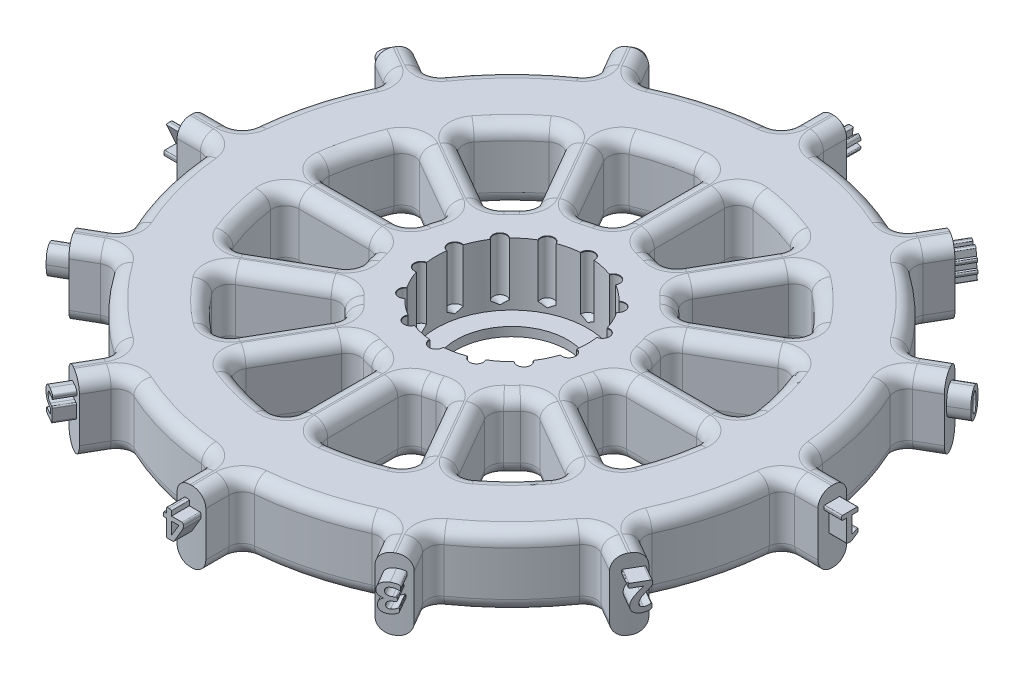
SolidWorks part; units mm, degrees
note: '?' marks a value the reader was unsure of.
ref_plane "Front Plane" through (0, 0, 0) normal (0, 0, 1) x (1, 0, 0)
ref_plane "Top Plane" through (0, 0, 0) normal (0, 1, 0) x (1, 0, 0)
ref_plane "Right Plane" through (0, 0, 0) normal (1, 0, 0) x (0, 0, -1)
sketch "Sketch1" plane through (0, 0, 0) normal (0, 1, 0) x (1, 0, 0)
  line L1 (1.6138, 23.9457) -> (1.6138, 6.038)
  line L4 (0, 36.7262) -> (0, 36) construction
  line L5 (13.3705, 19.9306) -> (4.4167, 4.4222)
  line L6 (-1.6138, 23.9457) -> (-1.6138, 6.038)
  line L7 (1.6138, 31.9593) -> (1.6138, 35.9638)
  line L8 (-1.6138, 31.9593) -> (-1.6138, 35.9638)
  line L9 (10.5752, 21.5445) -> (1.6214, 6.036)
  line L10 (17.3773, 26.8706) -> (19.3795, 30.3387)
  line L11 (14.582, 28.4845) -> (16.5843, 31.9525)
  line L12 (21.5445, 10.5752) -> (6.036, 1.6214)
  line L13 (19.9306, 13.3705) -> (4.4222, 4.4167)
  line L14 (28.4845, 14.582) -> (31.9525, 16.5843)
  line L15 (26.8706, 17.3773) -> (30.3387, 19.3795)
  line L16 (23.9457, -1.6138) -> (6.038, -1.6138)
  line L17 (23.9457, 1.6138) -> (6.038, 1.6138)
  line L18 (31.9593, -1.6138) -> (35.9638, -1.6138)
  line L19 (31.9593, 1.6138) -> (35.9638, 1.6138)
  line L20 (19.9306, -13.3705) -> (4.4222, -4.4167)
  line L21 (21.5445, -10.5752) -> (6.036, -1.6214)
  line L22 (26.8706, -17.3773) -> (30.3387, -19.3795)
  line L23 (28.4845, -14.582) -> (31.9525, -16.5843)
  line L24 (10.5752, -21.5445) -> (1.6214, -6.036)
  line L25 (13.3705, -19.9306) -> (4.4167, -4.4222)
  line L26 (14.582, -28.4845) -> (16.5843, -31.9525)
  line L27 (17.3773, -26.8706) -> (19.3795, -30.3387)
  line L28 (-1.6138, -23.9457) -> (-1.6138, -6.038)
  line L29 (1.6138, -23.9457) -> (1.6138, -6.038)
  line L30 (-1.6138, -31.9593) -> (-1.6138, -35.9638)
  line L31 (1.6138, -31.9593) -> (1.6138, -35.9638)
  line L32 (-13.3705, -19.9306) -> (-4.4167, -4.4222)
  line L33 (-10.5752, -21.5445) -> (-1.6214, -6.036)
  line L34 (-17.3773, -26.8706) -> (-19.3795, -30.3387)
  line L35 (-14.582, -28.4845) -> (-16.5843, -31.9525)
  line L36 (-21.5445, -10.5752) -> (-6.036, -1.6214)
  line L37 (-19.9306, -13.3705) -> (-4.4222, -4.4167)
  line L38 (-28.4845, -14.582) -> (-31.9525, -16.5843)
  line L39 (-26.8706, -17.3773) -> (-30.3387, -19.3795)
  line L40 (-23.9457, 1.6138) -> (-6.038, 1.6138)
  line L41 (-23.9457, -1.6138) -> (-6.038, -1.6138)
  line L42 (-31.9593, 1.6138) -> (-35.9638, 1.6138)
  line L43 (-31.9593, -1.6138) -> (-35.9638, -1.6138)
  line L44 (-19.9306, 13.3705) -> (-4.4222, 4.4167)
  line L45 (-21.5445, 10.5752) -> (-6.036, 1.6214)
  line L46 (-26.8706, 17.3773) -> (-30.3387, 19.3795)
  line L47 (-28.4845, 14.582) -> (-31.9525, 16.5843)
  line L48 (-10.5752, 21.5445) -> (-1.6214, 6.036)
  line L49 (-13.3705, 19.9306) -> (-4.4167, 4.4222)
  line L50 (-14.582, 28.4845) -> (-16.5843, 31.9525)
  line L51 (-17.3773, 26.8706) -> (-19.3795, 30.3387)
  line L52 (1.6138, 23.9457) -> (1.6138, 6.038)
  circle A0 centre (0, 0) radius 36
  circle A1 centre (0, 0) radius 6.25
  circle A3 centre (0, 0) radius 32
  arc A5 (-1.6138, 6.038) -> (1.6138, 6.038) centre (0, 0) cw
  arc A6 (10.5752, 21.5445) -> (1.6138, 23.9457) centre (0, 0) ccw
  arc A7 (-1.6138, 31.9593) -> (1.6138, 31.9593) centre (0, 0) cw
  arc A8 (-1.6138, 35.9638) -> (1.6138, 35.9638) centre (0, 0) cw
  arc A9 (1.6214, 6.036) -> (4.4167, 4.4222) centre (0, 0) cw
  arc A11 (16.5843, 31.9525) -> (19.3795, 30.3387) centre (0, 0) cw
  arc A12 (14.582, 28.4845) -> (17.3773, 26.8706) centre (0, 0) cw
  arc A13 (4.4222, 4.4167) -> (6.036, 1.6214) centre (0, 0) cw
  arc A15 (30.3387, 19.3795) -> (31.9525, 16.5843) centre (0, 0) cw
  arc A16 (26.8706, 17.3773) -> (28.4845, 14.582) centre (0, 0) cw
  arc A17 (6.038, 1.6138) -> (6.038, -1.6138) centre (0, 0) cw
  arc A19 (35.9638, 1.6138) -> (35.9638, -1.6138) centre (0, 0) cw
  arc A20 (31.9593, 1.6138) -> (31.9593, -1.6138) centre (0, 0) cw
  arc A21 (6.036, -1.6214) -> (4.4222, -4.4167) centre (0, 0) cw
  arc A23 (31.9525, -16.5843) -> (30.3387, -19.3795) centre (0, 0) cw
  arc A24 (28.4845, -14.582) -> (26.8706, -17.3773) centre (0, 0) cw
  arc A25 (4.4167, -4.4222) -> (1.6214, -6.036) centre (0, 0) cw
  arc A27 (19.3795, -30.3387) -> (16.5843, -31.9525) centre (0, 0) cw
  arc A28 (17.3773, -26.8706) -> (14.582, -28.4845) centre (0, 0) cw
  arc A29 (1.6138, -6.038) -> (-1.6138, -6.038) centre (0, 0) cw
  arc A31 (1.6138, -35.9638) -> (-1.6138, -35.9638) centre (0, 0) cw
  arc A32 (1.6138, -31.9593) -> (-1.6138, -31.9593) centre (0, 0) cw
  arc A33 (-1.6214, -6.036) -> (-4.4167, -4.4222) centre (0, 0) cw
  arc A35 (-16.5843, -31.9525) -> (-19.3795, -30.3387) centre (0, 0) cw
  arc A36 (-14.582, -28.4845) -> (-17.3773, -26.8706) centre (0, 0) cw
  arc A37 (-4.4222, -4.4167) -> (-6.036, -1.6214) centre (0, 0) cw
  arc A39 (-30.3387, -19.3795) -> (-31.9525, -16.5843) centre (0, 0) cw
  arc A40 (-26.8706, -17.3773) -> (-28.4845, -14.582) centre (0, 0) cw
  arc A41 (-6.038, -1.6138) -> (-6.038, 1.6138) centre (0, 0) cw
  arc A43 (-35.9638, -1.6138) -> (-35.9638, 1.6138) centre (0, 0) cw
  arc A44 (-31.9593, -1.6138) -> (-31.9593, 1.6138) centre (0, 0) cw
  arc A45 (-6.036, 1.6214) -> (-4.4222, 4.4167) centre (0, 0) cw
  arc A47 (-31.9525, 16.5843) -> (-30.3387, 19.3795) centre (0, 0) cw
  arc A48 (-28.4845, 14.582) -> (-26.8706, 17.3773) centre (0, 0) cw
  arc A49 (-4.4167, 4.4222) -> (-1.6214, 6.036) centre (0, 0) cw
  arc A51 (-19.3795, 30.3387) -> (-16.5843, 31.9525) centre (0, 0) cw
  arc A52 (-17.3773, 26.8706) -> (-14.582, 28.4845) centre (0, 0) cw
  arc A53 (19.9306, 13.3705) -> (13.3705, 19.9306) centre (0, 0) ccw
  arc A54 (23.9457, 1.6138) -> (21.5445, 10.5752) centre (0, 0) ccw
  arc A55 (21.5445, -10.5752) -> (23.9457, -1.6138) centre (0, 0) ccw
  arc A56 (13.3705, -19.9306) -> (19.9306, -13.3705) centre (0, 0) ccw
  arc A57 (1.6138, -23.9457) -> (10.5752, -21.5445) centre (0, 0) ccw
  arc A58 (-10.5752, -21.5445) -> (-1.6138, -23.9457) centre (0, 0) ccw
  arc A59 (-19.9306, -13.3705) -> (-13.3705, -19.9306) centre (0, 0) ccw
  arc A60 (-23.9457, -1.6138) -> (-21.5445, -10.5752) centre (0, 0) ccw
  arc A61 (-21.5445, 10.5752) -> (-23.9457, 1.6138) centre (0, 0) ccw
  arc A62 (-13.3705, 19.9306) -> (-19.9306, 13.3705) centre (0, 0) ccw
  arc A63 (-1.6138, 23.9457) -> (-10.5752, 21.5445) centre (0, 0) ccw
  point P113 (0, 0)
  point P134 (0, 0)
  point P147 (0, 0)
  dimension "D1" = 72
  dimension "D2" = 12.5
  dimension "D3" = 12
  dimension "D4" = 12
  dimension "D5" = 9.3362
  dimension "D6" = 17.9076
extrude "Base Wheel" add sketch "Sketch1" along normal blind 8 contours A1 | A0
ref_axis "Axis1" through (0, -0.3931, 0) along (0, 1, 0)?
sketch "Sketch9" plane through (0, 8, 0) normal (0, 1, 0) x (1, 0, 0)
  line L1 (10.5752, 21.5445) -> (5.178, 12.1963)
  line L2 (1.5649, 23.9489) -> (1.5649, 13.1573)
  line L3 (13.3297, 19.9579) -> (7.9339, 10.6121)
  line L4 (19.9306, 13.3705) -> (10.5825, 7.9733)
  line L5 (21.5228, 10.6192) -> (12.177, 5.2234)
  line L6 (23.9457, 1.6138) -> (13.1514, 1.6138)
  line L7 (23.9489, -1.5649) -> (13.1573, -1.5649)
  line L8 (21.5445, -10.5752) -> (12.1963, -5.178)
  line L9 (19.9579, -13.3297) -> (10.6121, -7.9339)
  line L10 (13.3705, -19.9306) -> (7.9733, -10.5825)
  line L11 (10.6192, -21.5228) -> (5.2234, -12.177)
  line L12 (1.6138, -23.9457) -> (1.6138, -13.1514)
  line L13 (-1.5649, -23.9489) -> (-1.5649, -13.1573)
  line L14 (-10.5752, -21.5445) -> (-5.178, -12.1963)
  line L15 (-13.3297, -19.9579) -> (-7.9339, -10.6121)
  line L16 (-19.9306, -13.3705) -> (-10.5825, -7.9733)
  line L17 (-21.5228, -10.6192) -> (-12.177, -5.2234)
  line L18 (-23.9457, -1.6138) -> (-13.1514, -1.6138)
  line L19 (-23.9489, 1.5649) -> (-13.1573, 1.5649)
  line L20 (-21.5445, 10.5752) -> (-12.1963, 5.178)
  line L21 (-19.9579, 13.3297) -> (-10.6121, 7.9339)
  line L22 (-13.3705, 19.9306) -> (-7.9733, 10.5825)
  line L23 (-10.6192, 21.5228) -> (-5.2234, 12.177)
  line L24 (-1.6138, 23.9457) -> (-1.6138, 13.1514)
  line L25 (31.9593, -1.6138) -> (35.9638, -1.6138)
  line L26 (28.4845, -14.582) -> (31.9525, -16.5843)
  line L27 (17.3773, -26.8706) -> (19.3795, -30.3387)
  line L28 (26.8706, -17.3773) -> (30.3387, -19.3795)
  line L29 (1.6138, -31.9593) -> (1.6138, -35.9638)
  line L30 (14.582, -28.4845) -> (16.5843, -31.9525)
  line L31 (-14.582, -28.4845) -> (-16.5843, -31.9525)
  line L32 (-1.6138, -31.9593) -> (-1.6138, -35.9638)
  line L33 (-26.8706, -17.3773) -> (-30.3387, -19.3795)
  line L34 (-17.3773, -26.8706) -> (-19.3795, -30.3387)
  line L35 (-31.9593, -1.6138) -> (-35.9638, -1.6138)
  line L36 (-28.4845, -14.582) -> (-31.9525, -16.5843)
  line L37 (-28.4845, 14.582) -> (-31.9525, 16.5843)
  line L38 (-31.9593, 1.6138) -> (-35.9638, 1.6138)
  line L39 (-17.3773, 26.8706) -> (-19.3795, 30.3387)
  line L40 (-26.8706, 17.3773) -> (-30.3387, 19.3795)
  line L41 (-1.6138, 31.9593) -> (-1.6138, 35.9638)
  line L42 (-14.582, 28.4845) -> (-16.5843, 31.9525)
  line L43 (14.582, 28.4845) -> (16.5843, 31.9525)
  line L44 (1.6138, 31.9593) -> (1.6138, 35.9638)
  line L45 (26.8706, 17.3773) -> (30.3387, 19.3795)
  line L46 (17.3773, 26.8706) -> (19.3795, 30.3387)
  line L47 (31.9593, 1.6138) -> (35.9638, 1.6138)
  line L48 (28.4845, 14.582) -> (31.9525, 16.5843)
  arc A0 (10.5752, 21.5445) -> (1.5649, 23.9489) centre (0, 0) ccw
  arc A2 (5.178, 12.1963) -> (1.5649, 13.1573) centre (0, 0) ccw
  arc A3 (10.5825, 7.9733) -> (7.9339, 10.6121) centre (0, 0) ccw
  arc A4 (19.9306, 13.3705) -> (13.3297, 19.9579) centre (0, 0) ccw
  arc A5 (13.1514, 1.6138) -> (12.177, 5.2234) centre (0, 0) ccw
  arc A6 (23.9457, 1.6138) -> (21.5228, 10.6192) centre (0, 0) ccw
  arc A7 (12.1963, -5.178) -> (13.1573, -1.5649) centre (0, 0) ccw
  arc A8 (21.5445, -10.5752) -> (23.9489, -1.5649) centre (0, 0) ccw
  arc A9 (7.9733, -10.5825) -> (10.6121, -7.9339) centre (0, 0) ccw
  arc A10 (13.3705, -19.9306) -> (19.9579, -13.3297) centre (0, 0) ccw
  arc A11 (1.6138, -13.1514) -> (5.2234, -12.177) centre (0, 0) ccw
  arc A12 (1.6138, -23.9457) -> (10.6192, -21.5228) centre (0, 0) ccw
  arc A13 (-5.178, -12.1963) -> (-1.5649, -13.1573) centre (0, 0) ccw
  arc A14 (-10.5752, -21.5445) -> (-1.5649, -23.9489) centre (0, 0) ccw
  arc A15 (-10.5825, -7.9733) -> (-7.9339, -10.6121) centre (0, 0) ccw
  arc A16 (-19.9306, -13.3705) -> (-13.3297, -19.9579) centre (0, 0) ccw
  arc A17 (-13.1514, -1.6138) -> (-12.177, -5.2234) centre (0, 0) ccw
  arc A18 (-23.9457, -1.6138) -> (-21.5228, -10.6192) centre (0, 0) ccw
  arc A19 (-12.1963, 5.178) -> (-13.1573, 1.5649) centre (0, 0) ccw
  arc A20 (-21.5445, 10.5752) -> (-23.9489, 1.5649) centre (0, 0) ccw
  arc A21 (-7.9733, 10.5825) -> (-10.6121, 7.9339) centre (0, 0) ccw
  arc A22 (-13.3705, 19.9306) -> (-19.9579, 13.3297) centre (0, 0) ccw
  arc A23 (-1.6138, 13.1514) -> (-5.2234, 12.177) centre (0, 0) ccw
  arc A24 (-1.6138, 23.9457) -> (-10.6192, 21.5228) centre (0, 0) ccw
  arc A25 (31.9525, -16.5843) -> (35.9638, -1.6138) centre (0, 0) ccw
  arc A26 (28.4845, -14.582) -> (31.9619, -1.5615) centre (0, 0) ccw
  arc A27 (17.3773, -26.8706) -> (26.8991, -17.3332) centre (0, 0) ccw
  arc A28 (19.3795, -30.3387) -> (30.3387, -19.3795) centre (0, 0) ccw
  arc A29 (1.6138, -31.9593) -> (14.6286, -28.4605) centre (0, 0) ccw
  arc A30 (1.6138, -35.9638) -> (16.5843, -31.9525) centre (0, 0) ccw
  arc A31 (-14.582, -28.4845) -> (-1.5615, -31.9619) centre (0, 0) ccw
  arc A32 (-16.5843, -31.9525) -> (-1.6138, -35.9638) centre (0, 0) ccw
  arc A33 (-26.8706, -17.3773) -> (-17.3332, -26.8991) centre (0, 0) ccw
  arc A34 (-30.3387, -19.3795) -> (-19.3795, -30.3387) centre (0, 0) ccw
  arc A35 (-31.9593, -1.6138) -> (-28.4605, -14.6286) centre (0, 0) ccw
  arc A36 (-35.9638, -1.6138) -> (-31.9525, -16.5843) centre (0, 0) ccw
  arc A37 (-28.4845, 14.582) -> (-31.9619, 1.5615) centre (0, 0) ccw
  arc A38 (-31.9525, 16.5843) -> (-35.9638, 1.6138) centre (0, 0) ccw
  arc A39 (-17.3773, 26.8706) -> (-26.8991, 17.3332) centre (0, 0) ccw
  arc A40 (-19.3795, 30.3387) -> (-30.3387, 19.3795) centre (0, 0) ccw
  arc A41 (-1.6138, 31.9593) -> (-14.6286, 28.4605) centre (0, 0) ccw
  arc A42 (-1.6138, 35.9638) -> (-16.5843, 31.9525) centre (0, 0) ccw
  arc A43 (14.582, 28.4845) -> (1.5615, 31.9619) centre (0, 0) ccw
  arc A44 (16.5843, 31.9525) -> (1.6138, 35.9638) centre (0, 0) ccw
  arc A45 (26.8706, 17.3773) -> (17.3332, 26.8991) centre (0, 0) ccw
  arc A46 (30.3387, 19.3795) -> (19.3795, 30.3387) centre (0, 0) ccw
  arc A47 (31.9593, 1.6138) -> (28.4605, 14.6286) centre (0, 0) ccw
  arc A48 (35.9638, 1.6138) -> (31.9525, 16.5843) centre (0, 0) ccw
  point P52 (0, 0)
  point P115 (0, 0)
  circle M2 centre (0, 0) radius 36
  dimension "D1" = 12
  dimension "D2" = 12
extrude "Cut-Extrude11" cut sketch "Sketch9" against normal through all contours A37 L37 L38 M2 | A39 L39 L40 M2 | A41 L41 L42 M2 | A43 L43 L44 M2 | A45 L45 L46 M2 | A47 L47 L48 M2 | A26 L26 L25 M2 | A27 L27 L28 M2 | A29 L29 L30 M2 | A31 L31 L32 M2 | A33 L33 L34 M2 | A35 L35 L36 M2 | L20 A20 L19 A19 | L22 A22 L21 A21 | L24 A24 L23 A23 | A2 L1 A0 L2 | L4 A4 L3 A3 | L6 A6 L5 A5 | L8 A8 L7 A7 | L10 A10 L9 A9 | L12 A12 L11 A11 | L14 A14 L13 A13 | L16 A16 L15 A15 | L18 A18 L17 A17
fillet "Fillet1" radius 1.5 62 edges at (10.6719, 8, 15.2566) (-28.6046, 0, -18.3784) (-18.3784, 8, -28.6046) (-15.5831, 8, -30.2185) (15.5831, 0, -30.2185) (16.8704, 0, 7.8766) (30.2185, 0, -15.5831) (33.9615, 0, -1.6138) (-1.6138, 0, -18.5485) (-7.9213, 8, -16.8499) (-15.285, 8, -10.6318) (18.5485, 8, -1.6138) (10.6318, 0, -15.285) (1.5649, 0, -18.5531) (-18.5485, 0, 1.6138) (-10.6318, 8, 15.285) (-15.2566, 8, 10.6719) (-1.5649, 8, 18.5531) (-7.8766, 0, 16.8704) (1.6138, 8, 18.5485) (15.5831, 8, 30.2185) (-15.5831, 0, 30.2185) (-15.5831, 8, 30.2185) (-30.2185, 8, 15.5831) (-18.3784, 0, 28.6046) (-1.6138, 4, -13.1514) (-3.4531, 8, -12.7921) (23.9489, 4, 1.5649) (13.3705, 4, 19.9306) (-12.1963, 4, -5.178) (-9.3866, 0, -9.3517) (-31.9593, 4, -1.6138) (1.6138, 4, -31.9593) (9.3517, 0, -9.3866) (10.5825, 4, -7.9733) (9.3517, 8, -9.3866) (12.7921, 0, -3.4531) (6.2353, 0, 23.1759) (-19.9306, 4, 13.3705) (-23.1885, 0, -6.188) (-23.9489, 4, -1.5649) (28.4845, 4, -14.582) (30.9096, 8, -8.2822) (30.9096, 0, 8.2822) (28.4845, 4, 14.582) (22.6274, 0, 22.6274) (-6.2353, 0, -23.1759) (23.9457, 4, -1.6138) (23.1759, 0, -6.2353) (21.5228, 4, -10.6192) (1.5649, 4, -23.9489) (6.188, 8, -23.1885) (-12.7921, 8, 3.4531) (-7.9339, 4, 10.6121) (-9.3517, 0, 9.3866) (3.4531, 0, 12.7921) (3.4531, 8, 12.7921) (14.582, 4, 28.4845) (8.2822, 0, 30.9096) (-8.2822, 0, 30.9096) (-31.9593, 4, 1.6138) (-22.6274, 8, 22.6274)
ref_plane "Plane1" through (31.1769, 0, 18) normal (0.866, 0, 0.5) x (0.5, 0, -0.866)
sketch "Sketch10" plane through (31.1769, 0, 18) normal (0.866, 0, 0.5) x (0.5, 0, -0.866)
  line L0 (1.6138, 6.5) -> (-1.6138, 6.5) construction
  text T0 "2" font "Calibri" height 3
extrude "Boss-Extrude1" add sketch "Sketch10" along normal blind 2 separate body
ref_plane "Plane2" through (18, 0, 31.1769) normal (0.5, 0, 0.866) x (0.866, 0, -0.5)
sketch "Sketch11" plane through (18, 0, 31.1769) normal (0.5, 0, 0.866) x (0.866, 0, -0.5)
  line L0 (-1.6138, 6.5) -> (1.6138, 6.5) construction
  text T0 "3" font "Calibri" height 3
extrude "Boss-Extrude2" add sketch "Sketch11" along normal blind 2 separate body
ref_plane "Plane0" through (36, 0, 0) normal (-1, 0, 0) x (0, 0, 1)
sketch "Sketch13" plane through (36, 0, 0) normal (-1, 0, 0) x (0, 0, 1)
  line L0 (-1.6138, 6.5) -> (1.6138, 6.5) construction
  text T0 "1" font "Calibri" height 3
extrude "Boss-Extrude 0" add sketch "Sketch13" against normal blind 2
ref_plane "Plane3" through (0, 0, 36) normal (0, 0, 1) x (1, 0, 0)
sketch "Sketch14" plane through (0, 0, 36) normal (0, 0, 1) x (1, 0, 0)
  line L0 (1.561, 6.498) -> (-1.5601, 6.498) construction
  text T0 "4" font "Calibri" height 3
extrude "Boss-Extrude4" add sketch "Sketch14" along normal blind 2 separate body
ref_plane "Plane5" through (-18, 0, 31.1769) normal (-0.5, 0, 0.866) x (0.866, 0, 0.5)
sketch "Sketch16" plane through (-18, 0, 31.1769) normal (-0.5, 0, 0.866) x (0.866, 0, 0.5)
  line L0 (1.5511, 6.5) -> (-1.6162, 6.5) construction
  line L1 (-1.6138, 6.5) -> (-2.9744, 6.5) construction
  text T0 "5" font "Calibri" height 3
extrude "Boss-Extrude5" add sketch "Sketch16" along normal blind 2 separate body
ref_plane "Plane6" through (-31.1769, 0, 18) normal (-0.866, 0, 0.5) x (0.5, 0, 0.866)
sketch "Sketch18" plane through (-31.1769, 0, 18) normal (-0.866, 0, 0.5) x (0.5, 0, 0.866)
  line L0 (1.5176, 6.5) -> (-1.6405, 6.5) construction
  line L1 (-1.6138, 6.5) -> (-2.9744, 6.5) construction
  text T0 "6" font "Calibri" height 3
extrude "Boss-Extrude6" add sketch "Sketch18" along normal blind 2 separate body
ref_plane "Plane7" through (-36, 0, 0) normal (-1, 0, 0) x (0, 0, 1)
sketch "Sketch20" plane through (-36, 0, 0) normal (-1, 0, 0) x (0, 0, 1)
  line L0 (1.6138, 6.5) -> (-1.5835, 6.5) construction
  line L1 (-1.6138, 6.5) -> (-2.9744, 6.5) construction
  text T0 "7" font "Calibri" height 3
extrude "Boss-Extrude7" add sketch "Sketch20" along normal blind 2 separate body
ref_plane "Plane8" through (-31.1769, 0, -18) normal (-0.866, 0, -0.5) x (-0.5, 0, 0.866)
sketch "Sketch23" plane through (-31.1769, 0, -18) normal (-0.866, 0, -0.5) x (-0.5, 0, 0.866)
  line L0 (1.5944, 6.5) -> (-1.6269, 6.5) construction
  line L1 (-1.6138, 6.5) -> (-2.9744, 6.5) construction
  text T0 "8" font "Calibri" height 3
extrude "Boss-Extrude8" add sketch "Sketch23" along normal blind 2 separate body
ref_plane "Plane9" through (-18, 0, -31.1769) normal (-0.5, 0, -0.866) x (-0.866, 0, 0.5)
sketch "Sketch24" plane through (-18, 0, -31.1769) normal (-0.5, 0, -0.866) x (-0.866, 0, 0.5)
  line L0 (1.5359, 6.5) -> (-1.6222, 6.5) construction
  line L1 (-1.6138, 6.5) -> (-2.9744, 6.5) construction
  line L2 (2.9744, 6.5) -> (1.6138, 6.5) construction
  text T0 "9" font "Calibri" height 3
extrude "Boss-Extrude10" add sketch "Sketch24" along normal blind 2 separate body
ref_plane "Plane10" through (31.1769, 0, -18) normal (0.866, 0, -0.5) x (-0.5, 0, -0.866)
sketch "Sketch25" plane through (31.1769, 0, -18) normal (0.866, 0, -0.5) x (-0.5, 0, -0.866)
  line L0 (1.6138, 6.5) -> (-1.6138, 6.5) construction
  text T0 "0" font "Calibri" height 3
extrude "Boss-Extrude11" add sketch "Sketch25" along normal blind 2 separate body
ref_plane "Plane11" through (18, 0, -31.1769) normal (0.5, 0, -0.866) x (-0.866, 0, -0.5)
sketch "Sketch26" plane through (18, 0, -31.1769) normal (0.5, 0, -0.866) x (-0.866, 0, -0.5)
  line L0 (1.6138, 6.5) -> (-1.6138, 6.5) construction
  line L3 (-1.6138, 6.5) -> (-2.9744, 6.5) construction
  text T0 "#" font "Calibri" height 3
extrude "Boss-Extrude19" add sketch "Sketch26" along normal blind 2 separate body
ref_plane "Plane12" through (0, 0, -36) normal (0, 0, -1) x (-1, 0, 0)
sketch "Sketch28" plane through (0, 0, -36) normal (0, 0, -1) x (-1, 0, 0)
  line L0 (1.5945, 7.9854) -> (-1.6268, 7.9854) construction
  text T0 "*" font "Calibri" height 4
extrude "Boss-Extrude20" add sketch "Sketch28" along normal blind 2 separate body
sketch "Sketch34" plane through (0, 8, 0) normal (0, 1, 0) x (1, 0, 0)
  line L0 (0, 0) -> (0, 8.5) construction
  line L1 (0, 0) -> (3.688, 7.6582) construction
  line L2 (0, 0) -> (6.6456, 5.2997) construction
  line L3 (0, 0) -> (8.2869, 1.8914) construction
  line L4 (0, 0) -> (8.2869, -1.8914) construction
  line L5 (0, 0) -> (6.6456, -5.2997) construction
  line L6 (0, 0) -> (3.688, -7.6582) construction
  line L7 (0, 0) -> (0, -8.5) construction
  line L8 (0, 0) -> (-3.688, -7.6582) construction
  line L9 (0, 0) -> (-6.6456, -5.2997) construction
  line L10 (0, 0) -> (-8.2869, -1.8914) construction
  line L11 (0, 0) -> (-8.2869, 1.8914) construction
  line L12 (0, 0) -> (-6.6456, 5.2997) construction
  line L13 (0, 0) -> (-3.688, 7.6582) construction
  point P18 (0, 0)
  dimension "D1" = 14
ref_plane "Plane13" through (0, 8, 0) normal (0, 1, 0) x (1, 0, 0)
hole_wizard "Ø1.5 (1.5) Diameter Hole1" positions "3DSketch4" profile "Sketch35" hole size "Ø1.5" standard "ANSI Metric"
sketch3d "3DSketch4"
  point P0 (0, 8, -8.5)
  point P3 (3.688, 8, -7.6582)
  point P6 (6.6456, 8, -5.2997)
  point P9 (8.2869, 8, -1.8914)
  point P12 (8.2869, 8, 1.8914)
  point P15 (6.6456, 8, 5.2997)
  point P18 (3.688, 8, 7.6582)
  point P21 (0, 8, 8.5)
  point P24 (-3.688, 8, 7.6582)
  point P27 (-6.6456, 8, 5.2997)
  point P30 (-8.2869, 8, 1.8914)
  point P33 (-8.2869, 8, -1.8914)
  point P36 (-6.6456, 8, -5.2997)
  point P39 (-3.688, 8, -7.6582)
sketch "Sketch35" plane through (0, 8, -8.5) normal (1, 0, 0) x (0, 0, 1)
  line L0 (0, 0) -> (0, 6.4506)
  line L1 (0, 6.4506) -> (0.75, 6)
  line L2 (0.75, 6) -> (0.75, 0.0604)
  line L3 (0.75, 0.0604) -> (0.775, 0)
  line L5 (0.775, 0) -> (0, 0)
  line L6 (-0.75, 0.0604) -> (-0.775, 0) construction
  line L10 (0, 6.4506) -> (-0.75, 6) construction
  line L11 (0, -6.35) -> (0, 107.95) construction
  dimension "Hole Dia." = 1.5
  dimension "Hole Depth" = 6
  dimension "Near C'Sink Dia." = 1.55
  dimension "Near C'Sink Angle" = 45
  dimension "Drill Angle" = 118
sketch "Sketch2" plane through (0, 8, 0) normal (0, 1, 0) x (1, 0, 0)
  circle A0 centre (0, 0) radius 8.5
extrude "Cut-Extrude1" cut sketch "Sketch2" against normal blind 7 contours A0
